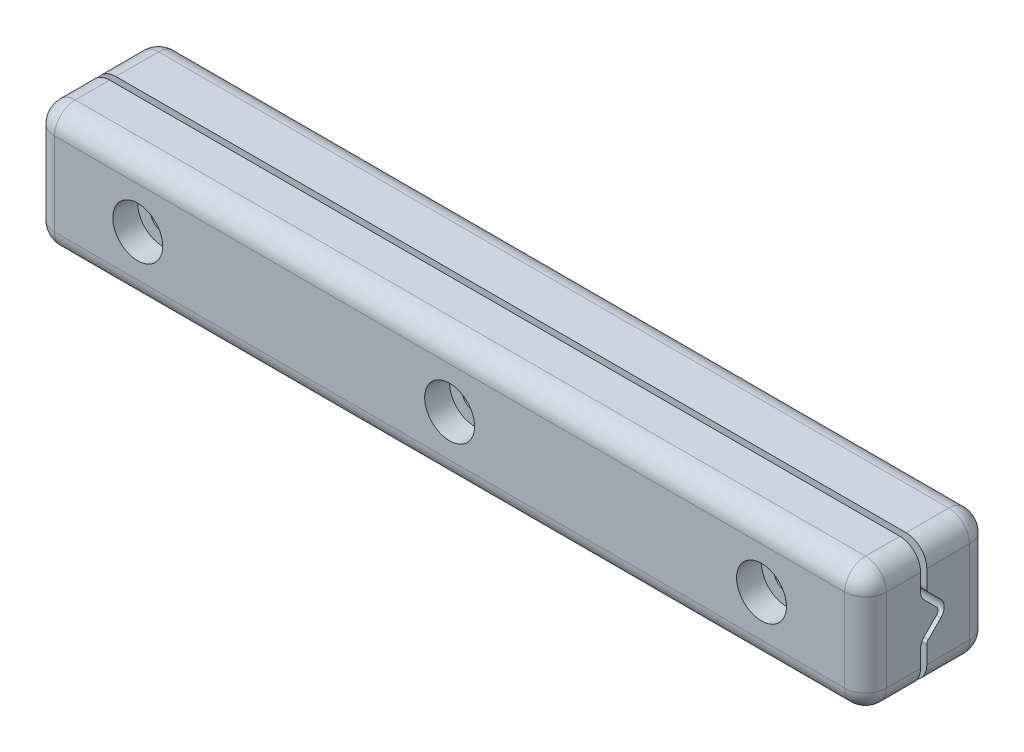
SolidWorks part; units mm, degrees
ref_plane "Спереди" through (0, 0, 0) normal (0, 0, 1) x (1, 0, 0)
ref_plane "Сверху" through (0, 0, 0) normal (0, 1, 0) x (1, 0, 0)
ref_plane "Справа" through (0, 0, 0) normal (1, 0, 0) x (0, 0, -1)
sketch "Эскиз1" plane through (0, 0, -1) normal (0, 0, 1) x (1, 0, 0)
  line L1 (-100, -15) -> (100, -15)
  line L2 (-100, -15) -> (-100, 15)
  line L3 (-100, 15) -> (100, 15)
  line L4 (100, -15) -> (100, 15)
  line L5 (0, 15) -> (0, -15) construction
  line L6 (-100, 0) -> (100, 0) construction
  point P0 (0, 0)
  point P8 (0, 0)
  dimension "D3" = 200
  dimension "D4" = 30
extrude "Бобышка-Вытянуть1" add sketch "Эскиз1" along normal mid plane 30
fillet "Скругление1" radius 5 12 edges at (0, -15, -16) (-100, -15, -1) (-100, 0, -16) (100, -15, -1) (100, 0, -16) (0, -15, 14) (-100, 0, 14) (100, 0, 14) (100, 15, -1) (0, 15, 14) (-100, 15, -1) (0, 15, -16)
sketch "Эскиз3" plane through (100, 0, 0) normal (1, 0, 0) x (0, 0, -1)
  line L54 (0.0555, 3.8839) -> (3.0555, 0.8839)
  line L55 (3.0555, -0.8839) -> (0.0555, -3.8839)
  line L56 (-0.75, -5.8284) -> (-0.75, -10)
  line L57 (-0.75, -10) -> (0.75, -10)
  line L58 (0.75, -10) -> (0.75, -5.8284)
  line L59 (1.1161, -4.9445) -> (4.1161, -1.9445)
  line L60 (4.1161, 1.9445) -> (1.1161, 4.9445)
  line L61 (0.75, 5.8284) -> (0.75, 10)
  line L62 (0.75, 10) -> (-0.75, 10)
  line L63 (-0.75, 10) -> (-0.75, 5.8284)
  line L64 (0.0555, 3.8839) -> (3.0555, 0.8839)
  line L65 (3.0555, -0.8839) -> (0.0555, -3.8839)
  line L66 (-0.75, -5.8284) -> (-0.75, -19.2901)
  line L67 (-0.75, -19.2901) -> (0.75, -19.2901)
  line L68 (0.75, -19.2901) -> (0.75, -5.8284)
  line L69 (1.1161, -4.9445) -> (4.1161, -1.9445)
  line L70 (4.1161, 1.9445) -> (1.1161, 4.9445)
  line L71 (0.75, 5.8284) -> (0.75, 19.7741)
  line L72 (0.75, 19.7741) -> (-0.75, 19.7741)
  line L73 (-0.75, 19.7741) -> (-0.75, 5.8284)
  arc A22 (3.0555, -0.8839) -> (3.0555, 0.8839) centre (2.1716, 0) ccw
  arc A23 (0.0555, -3.8839) -> (-0.75, -5.8284) centre (2, -5.8284) ccw
  arc A24 (1.1161, -4.9445) -> (0.75, -5.8284) centre (2, -5.8284) ccw
  arc A25 (4.1161, -1.9445) -> (4.1161, 1.9445) centre (2.1716, 0) ccw
  arc A26 (0.75, 5.8284) -> (1.1161, 4.9445) centre (2, 5.8284) ccw
  arc A27 (-0.75, 5.8284) -> (0.0555, 3.8839) centre (2, 5.8284) ccw
  arc A28 (3.0555, -0.8839) -> (3.0555, 0.8839) centre (2.1716, 0) ccw
  arc A29 (0.0555, -3.8839) -> (-0.75, -5.8284) centre (2, -5.8284) ccw
  arc A30 (1.1161, -4.9445) -> (0.75, -5.8284) centre (2, -5.8284) ccw
  arc A31 (4.1161, -1.9445) -> (4.1161, 1.9445) centre (2.1716, 0) ccw
  arc A32 (0.75, 5.8284) -> (1.1161, 4.9445) centre (2, 5.8284) ccw
  arc A33 (-0.75, 5.8284) -> (0.0555, 3.8839) centre (2, 5.8284) ccw
  dimension "D1" = 0
sketch "Эскиз4" plane through (0, 0, 14) normal (0, 0, 1) x (1, 0, 0)
  line L0 (-75, 0) -> (0, 0) construction
  line L3 (0, 0) -> (75, 0) construction
  line L4 (0, 10) -> (0, -10) construction
  line L5 (95, 10) -> (-95, 10) construction
  line L6 (-95, -10) -> (95, -10) construction
  circle A0 centre (0, 0) radius 3
  circle A1 centre (-75, 0) radius 3
  circle A2 centre (75, 0) radius 3
  dimension "D1" = 6
  dimension "D2" = 75
extrude "Вырез-Вытянуть8" cut sketch "Эскиз3" against normal through all
extrude "Вырез-Вытянуть4" cut sketch "Эскиз4" against normal through all
sketch "Эскиз7" plane through (0, 0, 14) normal (0, 0, 1) x (1, 0, 0)
  circle A2 centre (-75, 0) radius 6
  circle A3 centre (-75, 0) radius 6
  circle A5 centre (0, 0) radius 6
  circle A6 centre (0, 0) radius 6
  circle A8 centre (75, 0) radius 6
  circle A9 centre (75, 0) radius 6
  dimension "D3" = 3
extrude "Вырез-Вытянуть5" cut sketch "Эскиз7" against normal blind 6
sketch "Эскиз8" plane through (0, 0, -16) normal (0, 0, -1) x (-1, 0, 0)
  circle A2 centre (75, 0) radius 6
  circle A3 centre (75, 0) radius 6
  circle A5 centre (0, 0) radius 6
  circle A6 centre (0, 0) radius 6
  circle A8 centre (-75, 0) radius 6
  circle A9 centre (-75, 0) radius 6
  dimension "D3" = 3
extrude "Вырез-Вытянуть6" cut sketch "Эскиз8" against normal blind 6
equation "\"длина лезвия\"=900"
equation "\"радиус острия\"=3"
equation "\"длина острия\"=40"
equation "\"ширина лезвия\"=20"
equation "\"радиус сгиба\"=2"
equation "\"высота ребра жесткости\"=7"
equation "\"толщина лезвия \"=2"
equation "\"длина рукоятки\"=200"
equation "\"тлщина рукоятки\"=30"
equation "\"диаметр заклепки\"=6"
equation "\"расстояние между заклнпками\"=75"
equation "\"глубина заклепки\"=6"
equation "\"отступ от заклепки\"=3"
equation "\"диаметр шляпы\"=\"диаметр заклепки\" + 2*\"отступ от заклепки\""
equation "\"D3@Эскиз1\"=\"длина рукоятки\""
equation "\"D1@Эскиз4\"=\"диаметр заклепки\""
equation "\"D2@Эскиз4\"=\"расстояние между заклнпками\""
equation "\"D1@Эскиз7\"=\"отступ от заклепки\""
equation "\"D2@Эскиз7\"=\"отступ от заклепки\""
equation "\"D3@Эскиз7\"=\"отступ от заклепки\""
equation "\"D1@Бобышка-Вытянуть1\"=\"тлщина рукоятки\""
equation "\"D1@Вырез-Вытянуть5\"=\"глубина заклепки\""
equation "\"радиус скруглений\"=5"
equation "\"D1@Скругление1\"=\"радиус скруглений\""
equation "\"D1@Эскиз8\"=\"отступ от заклепки\""
equation "\"D2@Эскиз8\"=\"отступ от заклепки\""
equation "\"D3@Эскиз8\"=\"отступ от заклепки\""
equation "\"D1@Вырез-Вытянуть6\"=\"глубина заклепки\""
equation "\"высота головки\"=1.2"
equation "\"высота купола\"=3"
equation "\"D4@Эскиз1\"=\"ширина лезвия\"+10"
